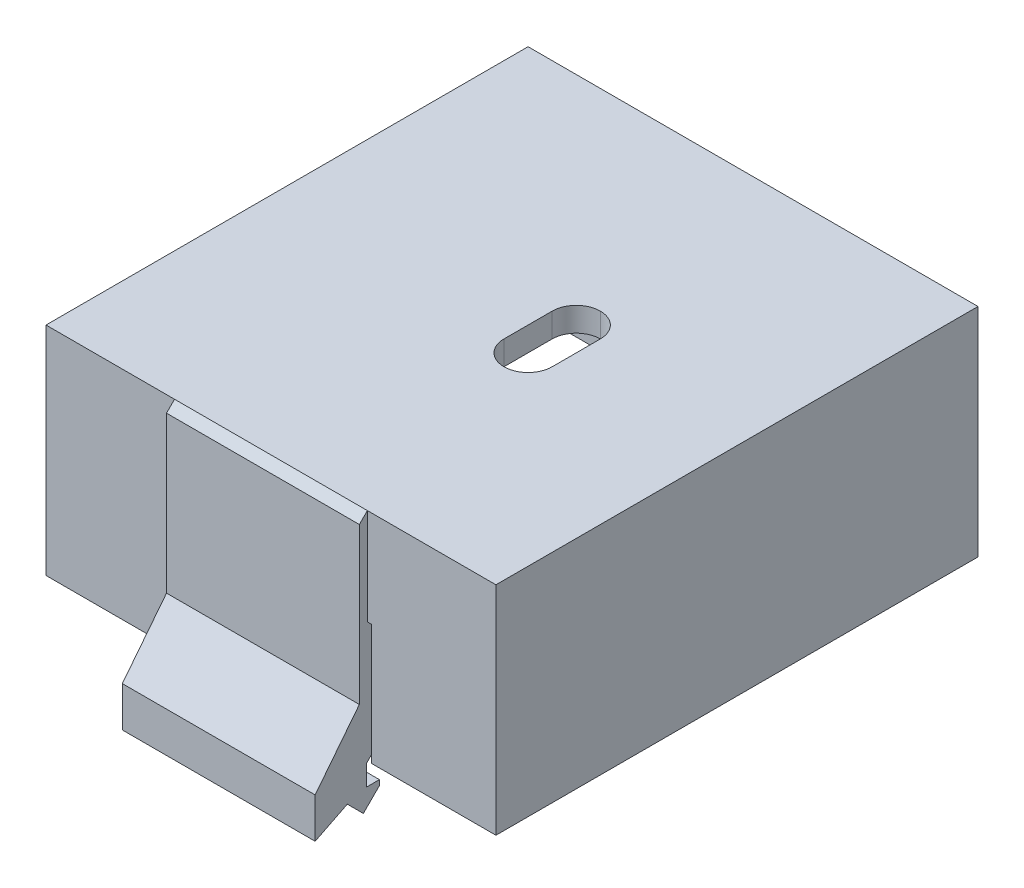
SolidWorks part; units mm, degrees
ref_plane "Front Plane" through (0, 0, 0) normal (0, 0, 1) x (1, 0, 0)
ref_plane "Top Plane" through (0, 0, 0) normal (0, 1, 0) x (1, 0, 0)
ref_plane "Right Plane" through (0, 0, 0) normal (1, 0, 0) x (0, 0, -1)
sketch "Sketch1" plane through (0, 9.8203, 0) normal (0, 1, 0) x (1, 0, 0)
  line L1 (-25, -27) -> (25, -27)
  line L2 (-25, -27) -> (-25, 27)
  line L3 (-25, 27) -> (25, 27)
  line L4 (25, -27) -> (25, 27)
  line L5 (-25, -27) -> (25, 27) construction
  line L6 (-25, 27) -> (25, -27) construction
  line L7 (-28, -30) -> (28, -30)
  line L8 (-28, -30) -> (-28, 30)
  line L9 (-28, 30) -> (28, 30)
  line L10 (28, -30) -> (28, 30)
  line L11 (-28, -30) -> (28, 30) construction
  line L12 (-28, 30) -> (28, -30) construction
  point P0 (0, 0)
  point P6 (25, 27)
  point P7 (0, 0)
extrude "Boss-Extrude1" add sketch "Sketch1" along normal offset from surface (24 mm away) 34 offset beyond the face yes
sketch "Sketch2" plane through (0, 33.8203, 0) normal (0, 1, 0) x (1, 0, 0)
  line L1 (28, -30) -> (-28, -30)
  line L2 (28, -30) -> (28, 30)
  line L3 (28, 30) -> (-28, 30)
  line L4 (-28, -30) -> (-28, 30)
  line L5 (28, -30) -> (-28, 30) construction
  line L6 (28, 30) -> (-28, -30) construction
  point P0 (0, 0)
extrude "Boss-Extrude2" add sketch "Sketch2" along normal blind 3
sketch "Sketch3" plane through (0, 0, 0) normal (1, 0, 0) x (0, 0, -1)
  line L0 (28.5, 9.8203) -> (28.5, 23.3203)
  line L1 (-30, 9.8203) -> (30, 9.8203) construction
  line L2 (28.5, 23.3203) -> (30, 24.8203)
  line L3 (30, 36.8203) -> (30, 9.8203) construction
  line L4 (30, 24.8203) -> (30, 9.8203)
  line L5 (30, 9.8203) -> (28.5, 9.8203)
  dimension "D1" = 1.5
  dimension "D2" = 45
  dimension "D3" = 15
extrude "Cut-Extrude1" cut sketch "Sketch3" against normal mid plane 25
sketch "Sketch4" plane through (0, 0, 0) normal (1, 0, 0) x (0, 0, -1)
  line L1 (30.1, 7.0703) -> (28.5, 7.0703)
  line L2 (28.5, 7.0703) -> (28.5, 6.4203)
  line L3 (28.5, 6.4203) -> (30.5, 4.4203)
  line L7 (31, 16.4203) -> (31, 35.8203)
  line L8 (28.5, 6.3203) -> (28.5, 7.3203) construction
  line L9 (28.5, 7.3203) -> (30, 7.3203) construction
  line L12 (30.5, 4.4203) -> (31.3531, 4.4203) construction
  line L14 (30, 4.8203) -> (28.5, 6.3203) construction
  line L15 (31, 35.8203) -> (30, 36.8203)
  line L16 (30, 36.8203) -> (29, 36.8203)
  line L18 (-30, 36.8203) -> (30, 36.8203) construction
  line L19 (30.1, 7.0703) -> (30.1, 9.6345)
  line L20 (30.1, 9.6345) -> (29, 10.7345)
  line L21 (29, 10.7345) -> (29, 36.8203)
  line L23 (30, 8.3203) -> (28.5, 9.8203) construction
  line L24 (30, 36.8203) -> (30, 9.8203) construction
  line L25 (30, 9.8203) -> (30, 1.8203) construction
  line L26 (30.5, 4.4203) -> (32.5, 6.4203)
  line L27 (32.5, 6.4203) -> (36.5, 4.4203)
  line L28 (36.5, 4.4203) -> (36.5, 9.4203)
  line L29 (36.5, 9.4203) -> (31, 16.4203)
  dimension "D2" = 0.25
  dimension "D3" = 0.1
  dimension "D4" = 1
  dimension "D5" = 0.5
  dimension "D6" = 0.5
  dimension "D7" = 0.1
  dimension "D8" = 5
  dimension "D9" = 1
  dimension "D10" = 45
  dimension "D11" = 6
  dimension "D12" = 45
  dimension "D13" = 2
  dimension "D14" = 7
extrude "Boss-Extrude3" add sketch "Sketch4" along normal mid plane 24
sketch "Sketch5" plane through (0, 9.8203, 0) normal (0, -1, 0) x (1, 0, 0)
  line L6 (26.7, -28.7) -> (-26.7, -28.7)
  line L7 (26.7, -28.7) -> (26.7, 28.7)
  line L8 (26.7, 28.7) -> (-26.7, 28.7)
  line L9 (-26.7, -28.7) -> (-26.7, 28.7)
  line L10 (26.7, -28.7) -> (-26.7, 28.7) construction
  line L11 (26.7, 28.7) -> (-26.7, -28.7) construction
  line L14 (25, -27) -> (-25, -27)
  line L15 (25, -27) -> (25, 27)
  line L16 (25, 27) -> (-25, 27)
  line L17 (-25, -27) -> (-25, 27)
  line L18 (25, -27) -> (-25, 27) construction
  line L19 (25, 27) -> (-25, -27) construction
  line L20 (-26.5, -28.5) -> (-26.5, 28.5) construction
  line L21 (-26.5, 28.5) -> (-12.5, 28.5) construction
  point P0 (0, 0)
  point P1 (0, 0)
  point P11 (0, 0)
  dimension "D1" = 0.2
  dimension "D2" = 0.2
extrude "Cut-Extrude2" cut sketch "Sketch5" against normal blind 5.5
mirror "Mirror1" about plane through (0, 0, 0) normal (0, 0, 1) of "Cut-Extrude1", "Boss-Extrude3"
sketch "Sketch6" plane through (0, 36.8203, 0) normal (0, 1, 0) x (1, 0, 0)
  line L1 (2, 6) -> (8, 6)
  line L2 (2, 6) -> (2, -6)
  line L3 (2, -6) -> (8, -6)
  line L4 (8, 6) -> (8, -6)
  line L5 (2, 6) -> (8, -6) construction
  line L6 (2, -6) -> (8, 6) construction
  point P0 (5, 0)
  dimension "D1" = 6
  dimension "D2" = 12
  dimension "D3" = 5
extrude "Cut-Extrude3" cut sketch "Sketch6" against normal up to next
fillet "Fillet3" radius 3 4 edges at (2, 35.3203, 6) (8, 35.3203, 6) (8, 35.3203, -6) (2, 35.3203, -6)
